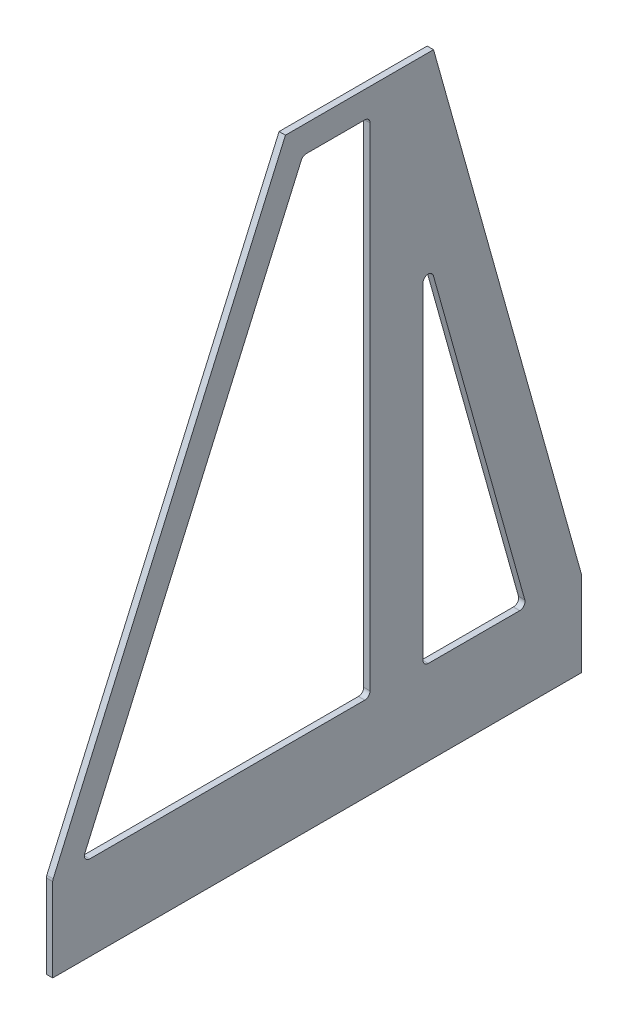
SolidWorks part; units mm, degrees
material "Клен"
ref_plane "Спереди" through (0, 0, 0) normal (0, 0, 1) x (1, 0, 0)
ref_plane "Сверху" through (0, 0, 0) normal (0, 1, 0) x (1, 0, 0)
ref_plane "Справа" through (0, 0, 0) normal (1, 0, 0) x (0, 0, -1)
sketch "боковина" plane through (0, 0, 0) normal (1, 0, 0) x (0, 0, -1)
  line L0 (-623.8462, -244.4615) -> (-123.8462, -244.4615)
  line L1 (-123.8462, -244.4615) -> (-123.8462, -165.1483)
  line L2 (-124.0313, -163.8002) -> (-263.8462, 335.5385)
  line L3 (-263.8462, 335.5385) -> (-313.8462, 335.5385)
  line L4 (-323.8462, 305.5385) -> (-323.8462, -159.4615)
  line L5 (-328.8462, -164.4615) -> (-588.8706, -164.4615)
  line L6 (-623.8462, -165.5129) -> (-623.8462, -244.4615)
  line L7 (-268.8462, -164.4615) -> (-182.3615, -164.4615)
  line L8 (-177.5467, -158.1134) -> (-264.0313, 150.7605)
  line L9 (-273.8462, 149.4123) -> (-273.8462, -159.4615)
  line L10 (-623.4227, -163.4992) -> (-403.8462, 335.5385)
  line L11 (-403.8462, 335.5385) -> (-313.8462, 335.5385)
  line L12 (-593.4471, -157.4478) -> (-388.8471, 307.5522)
  line L13 (-384.2706, 310.5385) -> (-328.8462, 310.5385)
  arc A0 (-264.0313, 150.7605) -> (-273.8462, 149.4123) centre (-268.8462, 149.4123) ccw
  arc A1 (-182.3615, -164.4615) -> (-177.5467, -158.1134) centre (-182.3615, -159.4615) ccw
  arc A2 (-268.8462, -164.4615) -> (-273.8462, -159.4615) centre (-268.8462, -159.4615) cw
  arc A3 (-323.8462, -159.4615) -> (-328.8462, -164.4615) centre (-328.8462, -159.4615) cw
  arc A4 (-593.4471, -157.4478) -> (-588.8706, -164.4615) centre (-588.8706, -159.4615) ccw
  arc A5 (-328.8462, 310.5385) -> (-323.8462, 305.5385) centre (-328.8462, 305.5385) cw
  arc A6 (-384.2706, 310.5385) -> (-388.8471, 307.5522) centre (-384.2706, 305.5385) ccw
  arc A7 (-623.4227, -163.4992) -> (-623.8462, -165.5129) centre (-618.8462, -165.5129) ccw
  arc A8 (-123.8462, -165.1483) -> (-124.0313, -163.8002) centre (-128.8462, -165.1483) ccw
  point P13 (-578.8956, -164.4615)
  point P15 (-398.8462, 335.5385)
  point P25 (-323.8462, -164.4615)
  point P34 (-623.8462, -164.4615)
  point P37 (-123.8462, -164.4615)
  point P38 (-358.8462, 335.5385)
  dimension "D10" = 5
  dimension "D11" = 5
  dimension "D12" = 5
  dimension "D1" = 80
  dimension "D2" = 60
  dimension "D6" = 300
  dimension "D7" = 50
  dimension "D8" = 50
  dimension "D4" = 500
  dimension "D5" = 80
  dimension "D3" = 200
  dimension "D9" = 25
  dimension "D13" = 80
  dimension "D14" = 25
extrude "Бобышка-боковина" add sketch "боковина" along normal blind 6
equation "\"D7@боковина\"=\"D8@боковина\""
equation "\"sheet_thickness\"= 6"
equation "\"bottom_line\"= 60"
equation "\"width_space\"= 500"
equation "\"D5@боковина\"=\"D1@боковина\""
